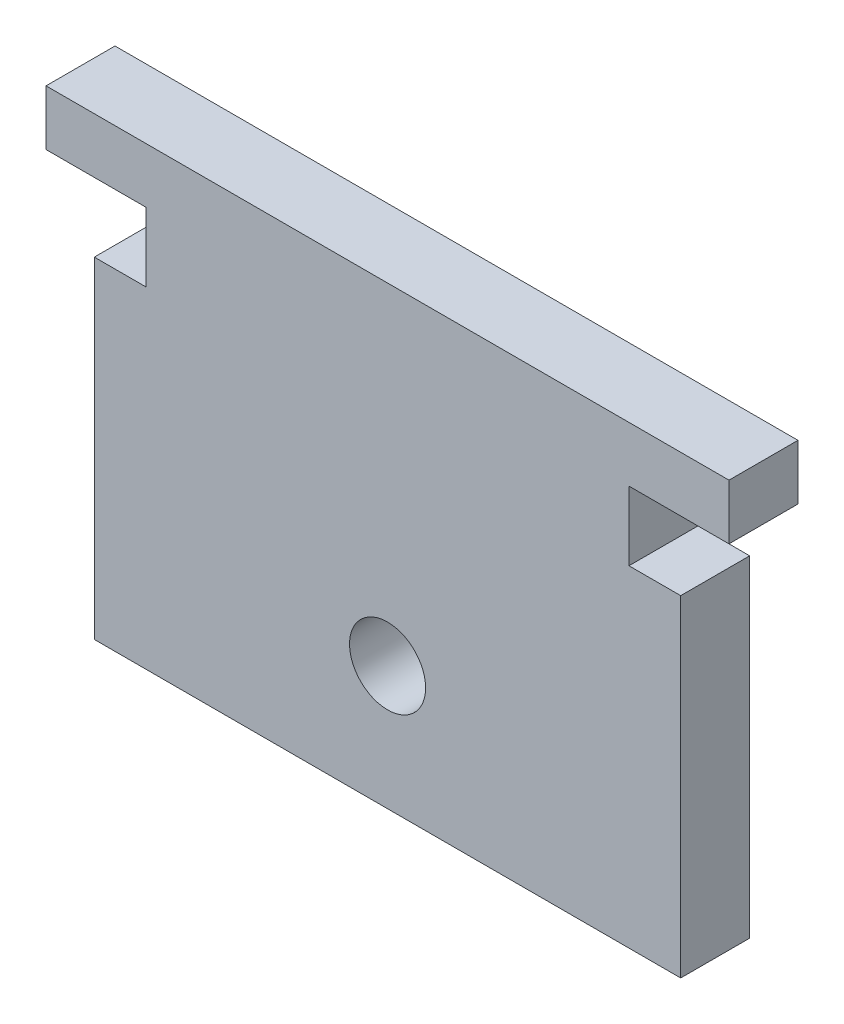
SolidWorks part; units mm, degrees
material "AISI 4130 Steel, annealed at 865C"
ref_plane "X-Y Datum" through (0, 0, 0) normal (0, 0, 1) x (1, 0, 0)
ref_plane "X-Z Datum" through (0, 0, 0) normal (0, 1, 0) x (1, 0, 0)
ref_plane "Y-Z Datum" through (0, 0, 0) normal (1, 0, 0) x (0, 0, -1)
sketch "Sketch1" plane through (0, 0, 0) normal (0, 0, 1) x (1, 0, 0)
  line L1 (-42.8625, -25.4) -> (42.8625, -25.4)
  line L2 (-42.8625, -25.4) -> (-42.8625, 25.4)
  line L3 (-42.8625, 25.4) -> (42.8625, 25.4)
  line L4 (42.8625, -25.4) -> (42.8625, 25.4)
  line L5 (-42.8625, -25.4) -> (42.8625, 25.4) construction
  line L6 (-42.8625, 25.4) -> (42.8625, -25.4) construction
  point P0 (0, 0)
  dimension "D1" = 85.725
  dimension "D2" = 50.8
extrude "Boss-Extrude1" add sketch "Sketch1" along normal blind 6.35
sketch "Sketch2" plane through (0, 0, 6.35) normal (0, 0, 1) x (1, 0, 0)
  line L1 (-42.8625, -25.4) -> (-26.9875, -25.4)
  line L2 (-42.8625, -25.4) -> (-42.8625, 17.78)
  line L3 (-42.8625, 17.78) -> (-26.9875, 17.78)
  line L4 (-26.9875, -25.4) -> (-26.9875, 17.78)
  line L5 (42.8625, -25.4) -> (26.9875, -25.4)
  line L6 (42.8625, -25.4) -> (42.8625, 17.78)
  line L7 (42.8625, 17.78) -> (26.9875, 17.78)
  line L8 (26.9875, -25.4) -> (26.9875, 17.78)
  dimension "D1" = 15.875
  dimension "D2" = 43.18
extrude "Cut-Extrude1" cut sketch "Sketch2" against normal blind 6.35
sketch "Sketch3" plane through (0, 25.4, 0) normal (0, 1, 0) x (1, 0, 0)
  line L1 (-42.8625, 0) -> (42.8625, 0)
  line L2 (-42.8625, 0) -> (-42.8625, -6.35)
  line L3 (-42.8625, -6.35) -> (42.8625, -6.35)
  line L4 (42.8625, 0) -> (42.8625, -6.35)
extrude "Cut-Extrude2" cut sketch "Sketch3" against normal blind 2.54
sketch "Sketch5" plane through (-26.9875, 0, 0) normal (-1, 0, 0) x (0, 0, 1)
  line L0 (6.35, -25.4) -> (6.35, 17.78) construction
  line L1 (0, 17.78) -> (6.35, 17.78)
  line L2 (0, 17.78) -> (0, 11.43)
  line L3 (0, 11.43) -> (6.35, 11.43)
  line L4 (6.35, 17.78) -> (6.35, 11.43)
  dimension "D1" = 6.35
extrude "Cut-Extrude3" cut sketch "Sketch5" against normal blind 4.7625
mirror "Mirror1" about plane through (0, 0, 0) normal (1, 0, 0) of "Cut-Extrude3"
sketch "Sketch6" plane through (0, 0, 6.35) normal (0, 0, 1) x (1, 0, 0)
  line L12 (26.9875, 11.43) -> (22.225, 11.43)
  line L13 (22.225, 11.43) -> (22.225, 17.78)
  line L14 (22.225, 17.78) -> (42.8625, 17.78)
  line L15 (42.8625, 17.78) -> (42.8625, 22.86)
  line L16 (42.8625, 22.86) -> (-42.8625, 22.86)
  line L17 (-42.8625, 22.86) -> (-42.8625, 17.78)
  line L18 (-42.8625, 17.78) -> (-22.225, 17.78)
  line L19 (-22.225, 17.78) -> (-22.225, 11.43)
  line L20 (-22.225, 11.43) -> (-26.9875, 11.43)
  line L21 (-26.9875, 11.43) -> (-26.9875, -25.4)
  line L22 (-26.9875, -25.4) -> (26.9875, -25.4)
  line L23 (26.9875, -25.4) -> (26.9875, 11.43)
  line L24 (26.9875, 11.43) -> (22.225, 11.43)
  line L25 (22.225, 11.43) -> (22.225, 17.78)
  line L26 (22.225, 17.78) -> (42.8625, 17.78)
  line L27 (42.8625, 17.78) -> (42.8625, 22.86)
  line L28 (42.8625, 22.86) -> (-42.8625, 22.86)
  line L29 (-42.8625, 22.86) -> (-42.8625, 17.78)
  line L30 (-42.8625, 17.78) -> (-22.225, 17.78)
  line L31 (-22.225, 17.78) -> (-22.225, 11.43)
  line L32 (-22.225, 11.43) -> (-26.9875, 11.43)
  line L33 (-26.9875, 11.43) -> (-26.9875, -25.4)
  line L34 (-26.9875, -25.4) -> (26.9875, -25.4)
  line L35 (26.9875, -25.4) -> (26.9875, 11.43)
  circle A1 centre (0.0059, -7.6663) radius 3.5
  dimension "D2" = 17.7337
  dimension "D1" = 0
extrude "Cut-Extrude4" cut sketch "Sketch6" against normal blind 6.35 contours A1 region at (0.0059, -7.6663, 6.35)
sketch "Sketch7" plane through (-42.8625, 0, 0) normal (-1, 0, 0) x (0, 0, 1)
  line L1 (0, 22.86) -> (6.35, 22.86)
  line L2 (0, 22.86) -> (0, 17.78)
  line L3 (0, 17.78) -> (6.35, 17.78)
  line L4 (6.35, 22.86) -> (6.35, 17.78)
extrude "Cut-Extrude5" cut sketch "Sketch7" against normal blind 11.43
mirror "Mirror2" about plane through (0, 0, 0) normal (1, 0, 0) of "Cut-Extrude5"
sketch "Sketch8" plane through (0, -25.4, 0) normal (0, -1, 0) x (1, 0, 0)
  line L7 (-26.9875, 6.35) -> (26.9875, 6.35)
  line L8 (-26.9875, 6.35) -> (-26.9875, 0)
  line L9 (-26.9875, 0) -> (26.9875, 0)
  line L10 (26.9875, 6.35) -> (26.9875, 0)
extrude "Cut-Extrude6" cut sketch "Sketch8" against normal blind 6.35
